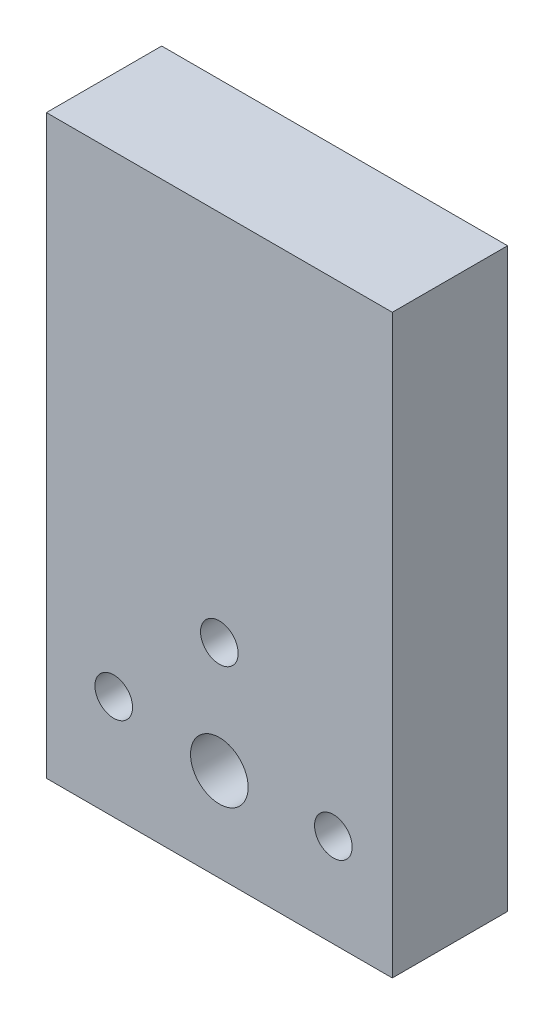
SolidWorks part; units mm, degrees
ref_plane "Front Plane" through (0, 0, 0) normal (0, 0, 1) x (1, 0, 0)
ref_plane "Top Plane" through (0, 0, 0) normal (0, 1, 0) x (1, 0, 0)
ref_plane "Right Plane" through (0, 0, 0) normal (1, 0, 0) x (0, 0, -1)
sketch "Sketch1" plane through (0, 0, 0) normal (0, 0, 1) x (1, 0, 0)
  line L1 (-15, 25) -> (15, 25)
  line L2 (-15, 25) -> (-15, -25)
  line L3 (-15, -25) -> (15, -25)
  line L4 (15, 25) -> (15, -25)
  line L5 (-15, 25) -> (15, -25) construction
  line L6 (-15, -25) -> (15, 25) construction
  circle A0 centre (0, -16.9357) radius 2.5
  point P0 (0, 0)
  point P8 (0, 0)
  dimension "D3" = 5
  dimension "D1" = 30
  dimension "D2" = 50
extrude "Boss-Extrude1" add sketch "Sketch1" along normal blind 10
hole_wizard "#4 Clearance Hole1" positions "Sketch2" profile "Sketch3" hole size "#4" standard "ANSI Inch" end condition up to next
sketch "Sketch2" plane through (0, 0, 10) normal (0, 0, 1) x (1, 0, 0)
  circle A0 centre (-0.2195, -10.7726) radius 17.57 construction
  point P0 (-9.1578, -15.9422)
  point P2 (9.8861, -16.9094)
  point P4 (0, -7.304)
  dimension "D1" = 35.14
sketch "Sketch3" plane through (-9.1578, -15.9422, 10) normal (1, 0, 0) x (0, -1, 0)
  line L0 (0, 0) -> (0, 10)
  line L1 (0, 10) -> (1.6319, 10)
  line L2 (1.6319, 10) -> (1.6319, 0)
  line L5 (1.6319, 0) -> (0, 0)
  line L11 (0, -6.35) -> (0, 107.95) construction
  dimension "Thru Hole Dia." = 3.2639
  dimension "Thru Hole Depth" = 10
